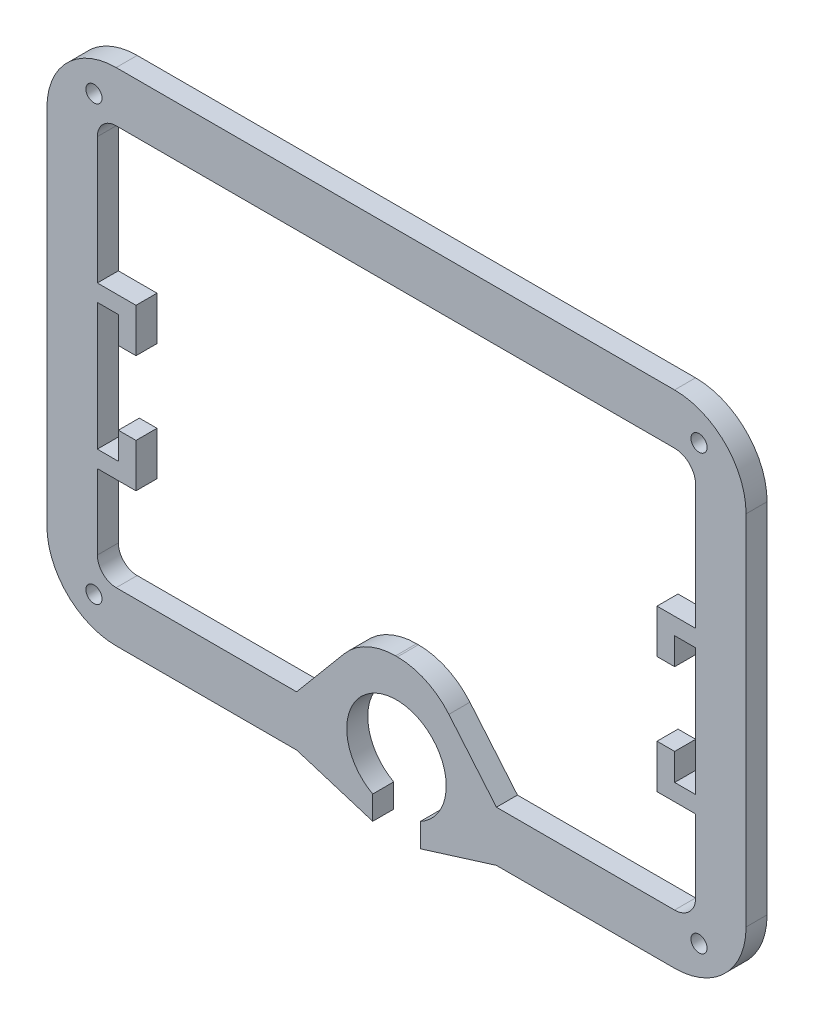
SolidWorks part; units mm, degrees
material "Delrin 2700 NC010, Low Viscosity Acetal Copolymer (SS)"
ref_plane "Front Plane" through (0, 0, 0) normal (0, 0, 1) x (1, 0, 0)
ref_plane "Top Plane" through (0, 0, 0) normal (0, 1, 0) x (1, 0, 0)
ref_plane "Right Plane" through (0, 0, 0) normal (1, 0, 0) x (0, 0, -1)
sketch "Sketch1" plane through (0, 0, 0) normal (0, 0, 1) x (1, 0, 0)
  line L0 (-21.1833, -18.923) -> (-7.5425, -18.923)
  line L1 (-22.606, 13.6903) -> (-22.606, -13.6903)
  line L2 (-21.1833, -15.113) -> (-7.5521, -15.113)
  line L3 (7.5521, -15.113) -> (21.0114, -15.113)
  line L4 (22.606, 13.5184) -> (22.606, -13.5184)
  line L5 (-1000, 0) -> (49000, 0) construction
  line L6 (-1.7968, -18.923) -> (-1.7968, -20.7107)
  line L7 (7.5425, -18.923) -> (21.0114, -18.923)
  line L8 (21.0114, 15.113) -> (-21.1833, 15.113)
  line L9 (-7.5521, -15.113) -> (-3.9596, -10.8316)
  line L10 (-26.416, 13.6903) -> (-26.416, -13.6903)
  line L11 (7.5521, -15.113) -> (3.9596, -10.8316)
  line L12 (-0.0681, -9.017) -> (0.0681, -9.017)
  line L13 (26.416, 13.5184) -> (26.416, -13.5184)
  line L14 (21.0114, 18.923) -> (-21.1833, 18.923)
  line L15 (1.7968, -18.923) -> (1.7968, -20.7107)
  line L16 (-7.5425, -18.923) -> (-1.7968, -20.7107)
  line L17 (7.5425, -18.923) -> (1.7968, -20.7107)
  line L18 (0, 12.5532) -> (0, -24.2768) construction
  line L19 (1.7968, -18.923) -> (21.0114, -18.923) construction
  line L20 (-21.1833, -18.923) -> (-1.7968, -18.923) construction
  line L21 (-22.606, 5.0849) -> (0, 5.0849) construction
  line L22 (0, 5.0849) -> (22.606, 5.0849) construction
  arc A0 (1.7968, -18.923) -> (-1.7968, -18.923) centre (0, -15.621) ccw
  arc A1 (-21.1833, -15.113) -> (-22.606, -13.6903) centre (-21.1833, -13.6903) cw
  arc A2 (-0.0681, -9.017) -> (-3.9596, -10.8316) centre (-0.0681, -14.097) ccw
  arc A3 (22.606, -13.5184) -> (21.0114, -15.113) centre (21.0114, -13.5184) cw
  arc A4 (21.0114, 15.113) -> (22.606, 13.5184) centre (21.0114, 13.5184) cw
  arc A5 (-21.1833, -18.923) -> (-26.416, -13.6903) centre (-21.1833, -13.6903) cw
  arc A6 (26.416, -13.5184) -> (21.0114, -18.923) centre (21.0114, -13.5184) cw
  arc A7 (21.0114, 18.923) -> (26.416, 13.5184) centre (21.0114, 13.5184) cw
  arc A8 (-21.1833, 18.923) -> (-26.416, 13.6903) centre (-21.1833, 13.6903) ccw
  circle A9 centre (-22.86, 16.383) radius 0.6096
  circle A10 centre (22.86, 16.383) radius 0.6096
  arc A11 (-21.1833, 15.113) -> (-22.606, 13.6903) centre (-21.1833, 13.6903) ccw
  arc A12 (0.0681, -9.017) -> (3.9596, -10.8316) centre (0.0681, -14.097) cw
  circle A13 centre (22.86, -16.383) radius 0.6096
  circle A14 centre (-22.86, -16.383) radius 0.6096
  circle A15 centre (0, -15.621) radius 5.3975 construction
  arc A18 (7.5521, -15.113) -> (-7.5521, -15.113) centre (0, -15.621) ccw construction
  point P0 (0, 0)
  dimension "D4" = 3.302
  dimension "D6" = 37.846
  dimension "D7" = 3.556
  dimension "D8" = 3.81
  dimension "D9" = 6.604
  dimension "D5" = 1.2192
  dimension "D2" = 45.212
  dimension "D3" = 7.5184
  dimension "D10" = 5.08
  dimension "D11" = 5.08
  dimension "D14" = 10.795
  dimension "D12" = 2.54
extrude "Boss-Extrude1" add sketch "Sketch1" along normal blind 1.5875
sketch "Sketch2" plane through (-22.606, 0, 0) normal (1, 0, 0) x (0, 0, -1)
  line L0 (0, 2.8448) -> (-1.5875, 2.8448)
  line L1 (0, -6.7596) -> (-1.5875, -6.7596) construction
  line L2 (-1.5875, -15.113) -> (0, -15.113)
  line L3 (-1.5875, -15.113) -> (0, -15.113) construction
  line L4 (0, -13.6903) -> (0, 13.6903)
  line L5 (0, 13.6903) -> (-1.5875, 13.6903)
  line L6 (-1.5875, 13.6903) -> (-1.5875, -13.6903)
  line L7 (0, 13.6903) -> (-1.5875, 13.6903)
  line L8 (0, -13.6903) -> (0, 4.1148)
  line L9 (-1.5875, -15.113) -> (-1.5875, -8.0296)
  line L10 (-1.5875, 4.1148) -> (-1.5875, -13.6903)
  line L11 (-1.5875, -13.6903) -> (0, -13.6903)
  line L12 (0, -15.113) -> (0, -8.0296)
  line L13 (0, 4.1148) -> (-1.5875, 4.1148)
  line L14 (-1.5875, 2.8448) -> (-1.5875, -6.6447)
  line L15 (-1.5875, 4.1148) -> (-1.5875, 2.8448)
  line L16 (0, 2.8448) -> (0, 4.1148)
  line L17 (0, -7.9147) -> (0, 1.4693)
  line L18 (-1.5875, -7.9147) -> (-1.5875, -6.6447)
  line L19 (0, -6.7596) -> (-1.5875, -6.7596)
  line L21 (0, -8.0296) -> (-1.5875, -8.0296)
  line L22 (0, -8.0296) -> (0, -13.6903)
  line L23 (-1.5875, -8.0296) -> (-1.5875, -13.6903)
  line L24 (47.9467, 2.8448) -> (-13.7896, 2.8448) construction
  line L28 (-1.5875, -13.6903) -> (0, -13.6903)
  line L29 (47.5608, -9.6909) -> (-13.8123, -5.9083) construction
  line M5 (0, -13.6903) -> (0, 13.6903)
  line M7 (-1.5875, 13.6903) -> (-1.5875, -13.6903)
  dimension "D1" = 0
  dimension "D2" = 1.27
  dimension "D4" = 1.27
extrude "Boss-Extrude2" add sketch "Sketch2" along normal blind 2.921 contours L13 L10 L0 M5 | L19 L17 L8 L0 L10 M7 | L21 L8 L19 L18 M5 M7 region at (-22.606, -1.9574, 0.7937) region at (-22.606, 3.4798, 0.7937) region at (-22.606, -7.3946, 0.7937)
extrude "Cut-Extrude1" cut sketch "Sketch2<3>" along normal blind 1.5875 contours L19 L17 L0 M5 M7 region at (-22.606, -1.9574, 0.7937)
sketch "Sketch2<3>" plane through (-22.606, 0, 0) normal (1, 0, 0) x (0, 0, -1) same geometry as "Sketch2"
sketch "Sketch3" plane through (-21.0185, 0, 0) normal (-1, 0, 0) x (0, 0, 1)
  line L0 (0, 2.8448) -> (1.5875, 2.8448) construction
  line L1 (0, -6.7596) -> (1.5875, -6.7596) construction
  line L2 (0, 2.8448) -> (1.5875, 2.8448)
  line L3 (0, -6.7596) -> (1.5875, -6.7596)
  line L4 (0, 0.8128) -> (1.5875, 0.8128)
  line L5 (0, -4.7276) -> (1.5875, -4.7276)
  line L6 (1.5875, 0.8128) -> (1.5875, -4.7276)
  line L7 (0, -4.7276) -> (0, 0.8128)
  line M2 (1.5875, -6.7596) -> (1.5875, 2.8448)
  line M4 (0, 2.8448) -> (0, -6.7596)
  dimension "D1" = 2.032
  dimension "D2" = 2.032
extrude "Cut-Extrude2" cut sketch "Sketch3" against normal up to surface (1.3335 mm away) contours L5 L4 M4 M2 region at (-21.0185, -1.9574, 0.7937) up to face at (-19.685, -1.9574, 0.7937)
mirror "Mirror1" about plane through (0, 0, 0) normal (1, 0, 0) of "Cut-Extrude2", "Boss-Extrude2", "Cut-Extrude1"
